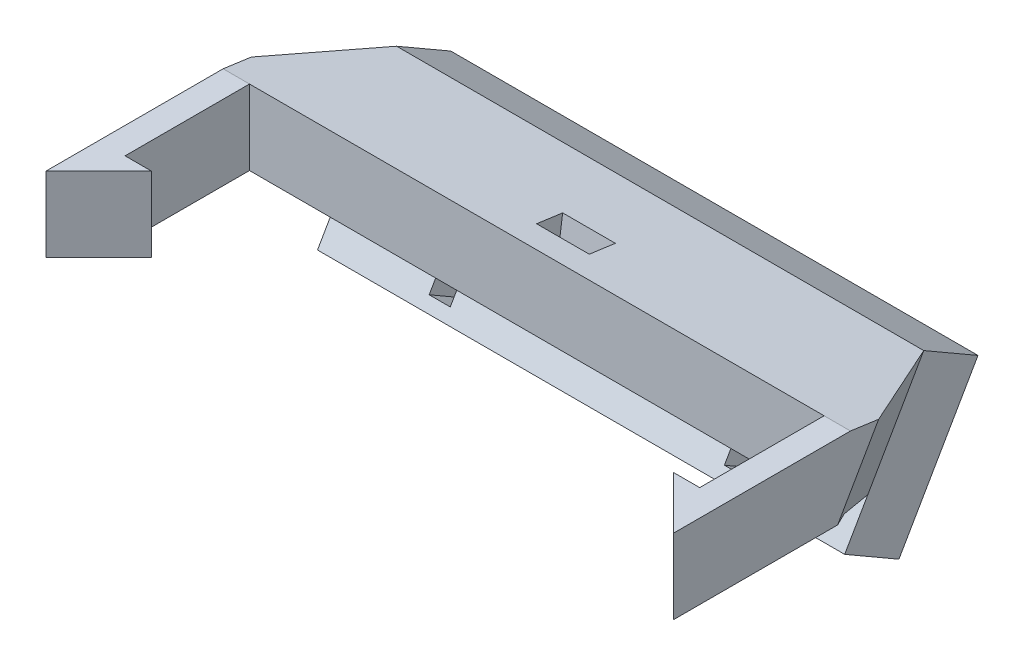
SolidWorks part; units mm, degrees
ref_plane "Front Plane" through (0, 0, 0) normal (0, 0, 1) x (1, 0, 0)
ref_plane "Top Plane" through (0, 0, 0) normal (0, 1, 0) x (1, 0, 0)
ref_plane "Right Plane" through (0, 0, 0) normal (1, 0, 0) x (0, 0, -1)
sketch "Sketch1" plane through (0, 0, 0) normal (0, 0, 1) x (1, 0, 0)
  line L1 (-37.7825, 17.78) -> (37.7825, 17.78)
  line L2 (-37.7825, 17.78) -> (-37.7825, -17.78)
  line L3 (-37.7825, -17.78) -> (37.7825, -17.78)
  line L4 (37.7825, 17.78) -> (37.7825, -17.78)
  point P4 (0, 17.78)
  point P6 (-37.7825, 0)
  dimension "D1" = 75.565
extrude "Boss-Extrude1" add sketch "Sketch1" against normal blind 3.175
sketch "Sketch6" plane through (0, 0, 0) normal (0, 0, 1) x (1, 0, 0)
  line L0 (-37.7825, 17.78) -> (-37.7825, -17.78) construction
  line L1 (-37.7825, 4.5142) -> (-34.6075, 4.5142)
  line L2 (-37.7825, 4.5142) -> (-37.7825, -4.5142)
  line L3 (-37.7825, -4.5142) -> (-34.6075, -4.5142)
  line L4 (-34.6075, 4.5142) -> (-34.6075, -4.5142)
  line L5 (37.7825, -17.78) -> (37.7825, 17.78) construction
  line L6 (37.7825, 4.5142) -> (34.6075, 4.5142)
  line L7 (37.7825, 4.5142) -> (37.7825, -4.5142)
  line L8 (37.7825, -4.5142) -> (34.6075, -4.5142)
  line L9 (34.6075, 4.5142) -> (34.6075, -4.5142)
  point P12 (37.7825, 0)
  point P14 (-37.7825, 0)
  dimension "D1" = 3.175
  dimension "D2" = 3.175
  dimension "D3" = 69.215
extrude "Boss-Extrude4" add sketch "Sketch6" along normal blind 14.986
sketch "Sketch8" plane through (0, -4.5142, 0) normal (0, -1, 0) x (1, 0, 0)
  line L0 (-37.7825, 14.986) -> (-31.4325, 14.986)
  line L1 (-31.4325, 14.986) -> (-37.7825, 21.336)
  line L2 (-37.7825, 21.336) -> (-37.7825, 14.986)
  line L3 (37.7825, 14.986) -> (31.4325, 14.986)
  line L4 (31.4325, 14.986) -> (37.7825, 21.336)
  line L5 (37.7825, 21.336) -> (37.7825, 14.986)
  dimension "D1" = 6.35
  dimension "D2" = 6.35
  dimension "D3" = 6.35
  dimension "D4" = 6.35
extrude "Boss-Extrude6" add sketch "Sketch8" against normal up to surface (9.0284 mm away) up to face at (-36.195, 4.5142, 7.493)
sketch "Sketch9" plane through (-37.7825, 0, 0) normal (-1, 0, 0) x (0, 0, 1)
  line L0 (-3.175, 17.78) -> (-18.5729, 8.89)
  line L1 (-18.5729, 8.89) -> (-3.175, -17.78)
  line L3 (-3.175, 17.78) -> (-3.175, -17.78) construction
  line L12 (0, 4.5142) -> (0, 17.78)
  line L13 (0, 17.78) -> (-3.175, 17.78)
  line L14 (-3.175, 17.78) -> (-3.175, -17.78)
  line L15 (-3.175, -17.78) -> (0, -17.78)
  line L16 (0, -17.78) -> (0, -4.5142)
  line L17 (0, -4.5142) -> (21.336, -4.5142)
  line L18 (21.336, -4.5142) -> (21.336, 4.5142)
  line L19 (21.336, 4.5142) -> (0, 4.5142)
  line L22 (-3.175, 17.78) -> (-3.175, -17.78)
  dimension "D1" = 90
  dimension "D2" = 30
  dimension "D3" = 0
extrude "Boss-Extrude7" add sketch "Sketch9" against normal up to surface (75.565 mm away) up to face at (37.7825, 0, 4.5403)
sketch "Sketch10" plane through (0, -5.8198, -10.0802) normal (0, -0.5, -0.866) x (-1, 0, 0)
  line L0 (37.7825, 16.9854) -> (37.7825, -13.8104) construction
  line L1 (-37.7825, -13.8104) -> (37.7825, -13.8104)
  line L2 (-37.7825, -13.8104) -> (-37.7825, 9.5576)
  line L3 (-37.7825, 9.5576) -> (37.7825, 9.5576)
  line L4 (37.7825, -13.8104) -> (37.7825, 9.5576)
  dimension "D1" = 23.368
extrude "Boss-Extrude8" add sketch "Sketch10" along normal blind 7.5452
sketch "Sketch11" plane through (-37.7825, 0, 0) normal (-1, 0, 0) x (0, 0, 1)
  line L0 (-14.859, 2.4573) -> (0, 4.5142)
  line L1 (0, 4.5142) -> (36.8887, 18.2755)
  line L2 (36.8887, 18.2755) -> (5.2861, 25.1503)
  line L3 (5.2861, 25.1503) -> (-30.3838, 8.2332)
  line L4 (-30.3838, 8.2332) -> (-14.859, 2.4573)
  line L5 (-3.175, -17.78) -> (-8.1255, -9.2055)
  line L6 (-8.1255, -9.2055) -> (0, -4.5142)
  line L7 (0, -4.5142) -> (40.1585, -20.4064)
  line L8 (40.1585, -20.4064) -> (15.5997, -25.3949)
  line L9 (15.5997, -25.3949) -> (-3.175, -17.78)
  line L10 (-9.7093, -21.5526) -> (-21.3933, -1.3153) construction
  line L11 (-9.7093, -21.5526) -> (-3.175, -17.78) construction
extrude "Cut-Extrude1" cut sketch "Sketch11" against normal through all
sketch "Sketch12" plane through (0, 4.4293, -0.6131) normal (0, 0.9906, -0.1371) x (1, 0, 0)
  line L0 (34.6075, -0.619) -> (-34.6075, -0.619) construction
  line L1 (-3.175, 5.731) -> (3.175, 5.731)
  line L2 (-3.175, 5.731) -> (-3.175, 2.556)
  line L3 (-3.175, 2.556) -> (3.175, 2.556)
  line L4 (3.175, 5.731) -> (3.175, 2.556)
  point P6 (0, 2.556)
  point P7 (0, -0.619)
  dimension "D1" = 3.175
  dimension "D2" = 6.35
  dimension "D3" = 3.175
extrude "Cut-Extrude2" cut sketch "Sketch12" against normal up to next and the other way through all
sketch "Sketch13" plane through (0, 8.2771, -4.7788) normal (0, 0.866, -0.5) x (1, 0, 0)
  line L0 (0, 11.6396) -> (0, 19.1848) construction
  line L1 (-37.7825, 11.6396) -> (37.7825, 11.6396) construction
  line L2 (-37.7825, 19.1848) -> (37.7825, 19.1848) construction
  line L3 (-31.75, 11.6396) -> (-37.7825, 0.9179)
  line L4 (-37.7825, 19.1848) -> (-31.75, 19.1848)
  line L5 (-37.7825, 19.1848) -> (-37.7825, 11.6396)
  line L6 (37.7825, 0.9179) -> (37.7825, 11.6396)
  line L7 (-31.75, 19.1848) -> (-31.75, 11.6396)
  line L8 (-37.7825, 0.9179) -> (-37.7825, 11.6396)
  line L9 (37.7825, 19.1848) -> (37.7825, 11.6396)
  line L10 (37.7825, 19.1848) -> (31.75, 19.1848)
  line L11 (31.75, 11.6396) -> (37.7825, 0.9179)
  line L12 (31.75, 19.1848) -> (31.75, 11.6396)
  line L13 (-37.7825, 11.6396) -> (-37.7825, -2.2571) construction
  point P12 (-31.75, 15.4122)
  dimension "D1" = 63.5
  dimension "D2" = 3.175
extrude "Cut-Extrude3" cut sketch "Sketch13" against normal through all
sketch "Sketch14" plane through (0, -9.5924, -16.6145) normal (0, -0.5, -0.866) x (-1, 0, 0)
  line L0 (-31.75, -4.1779) -> (31.75, -4.1779) construction
  line L1 (-31.75, -13.8104) -> (-31.75, 9.5576) construction
  line L2 (0, -4.1779) -> (0, -13.8104) construction
  line L3 (-19.05, -4.1779) -> (-16.51, -4.1779)
  line L4 (-19.05, -4.1779) -> (-19.05, -7.9879)
  line L5 (-19.05, -7.9879) -> (-16.51, -7.9879)
  line L6 (-16.51, -4.1779) -> (-16.51, -7.9879)
  line L7 (-31.75, -13.8104) -> (31.75, -13.8104) construction
  line L8 (19.05, -4.1779) -> (16.51, -4.1779)
  line L9 (16.51, -4.1779) -> (16.51, -7.9879)
  line L10 (19.05, -7.9879) -> (16.51, -7.9879)
  line L11 (19.05, -4.1779) -> (19.05, -7.9879)
  line L12 (-25.4, -11.0373) -> (0, -11.0373) construction
  dimension "D1" = 2.54
  dimension "D2" = 3.81
  dimension "D3" = 25.4
  dimension "D4" = 6.35
extrude "Cut-Extrude4" cut sketch "Sketch14" against normal up to next
sketch "Sketch15" plane through (0, -9.5924, -16.6145) normal (0, -0.5, -0.866) x (-1, 0, 0)
  line L0 (31.75, 9.5576) -> (-31.75, 9.5576) construction
  line L1 (-65.0097, -9.4924) -> (49.6515, -9.4924)
  line L2 (-65.0097, -9.4924) -> (-65.0097, -16.0708)
  line L3 (-65.0097, -16.0708) -> (49.6515, -16.0708)
  line L4 (49.6515, -9.4924) -> (49.6515, -16.0708)
  dimension "D1" = 19.05
extrude "Cut-Extrude5" cut sketch "Sketch15" against normal up to next
